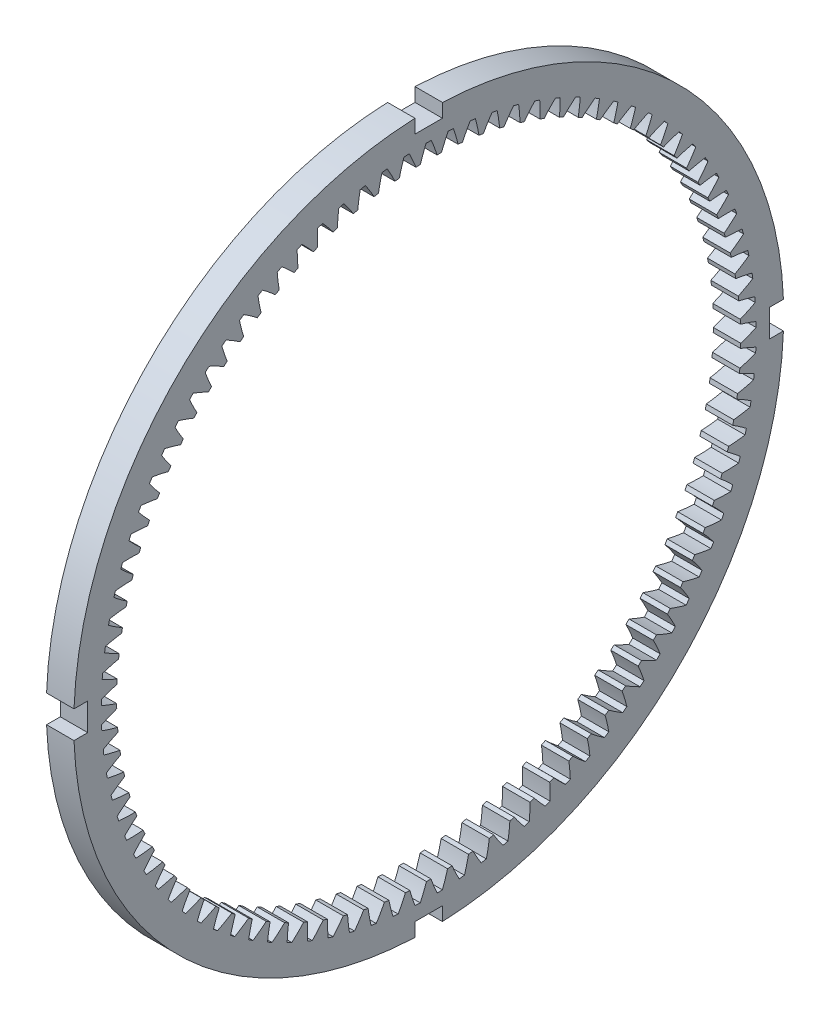
SolidWorks part; units mm, degrees
ref_plane "Plane1" through (0, 0, 0) normal (0, 0, 1) x (1, 0, 0)
ref_plane "Plane2" through (0, 0, 0) normal (0, 1, 0) x (1, 0, 0)
ref_plane "Plane3" through (0, 0, 0) normal (1, 0, 0) x (0, 0, -1)
sketch "HoldingSke" plane through (0, 0, 0) normal (0, 1, 0) x (1, 0, 0)
  line L0 (0, 0) -> (-0.0209, -0.3995)
  line L1 (-15, 0) -> (100, 0) construction
  line L2 (0, 0) -> (-2.1039, 2.3779)
  line L3 (0, 0) -> (-11.863, 4.5341)
  line L4 (0, 0) -> (-0.452, 8.6242)
  line L5 (0, 0) -> (-23.7986, -8.8762)
  line L6 (0, 0) -> (-10.5278, -7.1032)
  line L7 (-2.1039, 2.3779) -> (3.3635, 27.1825)
  line L8 (-76.2, 4.8779) -> (-54.61, 4.8779)
  line L9 (-71.009, 38.7566) -> (-53.1078, 45.2721)
  line L10 (-76.2, 71.12) -> (104.1128, 71.12)
  line L11 (0, 0) -> (-30, 0)
  line L12 (-76.2, 101.6) -> (-76.113, 101.6)
  line L13 (24.9733, 27.94) -> (52.9518, 28.4284)
  line L14 (24.9733, 27.94) -> (24.9743, 27.94)
  line L15 (24.9733, 27.94) -> (100.4006, 29.5858)
  circle A0 centre (0, 0) radius 50
  circle A1 centre (0, 0) radius 12.7
  circle A2 centre (0, 0) radius 12.7
  dimension "MHD" = 25.4
  dimension "Hub_dia" = 25.4
  dimension "Diameter" = 100
  dimension "Num_teeth" = 93
  dimension "Pitch" = 0.4
  dimension "Overall_len" = 25.4
  dimension "Show_teeth" = 93
  dimension "Thickness" = 12.7
  dimension "OAL" = 25.4001
  dimension "T_dim" = 21.59
  dimension "Ap" = 20
  dimension "H" = 19.05
  dimension "Pitch_radius" = 180.3128
  dimension "Width" = 30
  dimension "Backlash" = 0.087
  dimension "Addendum_fac" = 1
  dimension "Dedendum_fac" = 1.25
  dimension "Clearance_fac" = 0.25
  dimension "Dedendum_add" = 0.001
  dimension "Module" = 2.5
sketch "BasProSke" plane through (0, 0, 0) normal (0, 1, 0) x (1, 0, 0)
  line L0 (-10, 0) -> (60, 0) construction
  line L1 (0, 113.75) -> (0, 119.4014)
  line L2 (0, 113.75) -> (30, 113.75)
  line L3 (30, 113.75) -> (30, 119.4014)
  line L4 (30, 119.4014) -> (0, 119.4014)
  dimension "Thickness" = 30
  dimension "Diameter" = 238.8028
  dimension "Inside_diameter" = 227.5
revolve "Base-Revolve" add sketch "BasProSke" angle 360 about L0
sketch "TooCutSke" plane through (0, 0, 0) normal (1, 0, 0) x (0, 0, -1)
  line L3 (2.1809, 116.2295) -> (2.1809, 53.6633) construction
  line L4 (0, 0) -> (0, 59.563) construction
  line L5 (0, 0) -> (-2.3077, 68.2885) construction
  line L6 (-52.5279, 96.5964) -> (34.5007, 99.5374) construction
  circle A0 centre (0, 0) radius 116.25 construction
  circle A1 centre (0, 0) radius 119.376 construction
  circle A2 centre (0, 0) radius 98.3153 construction
  circle A3 centre (0, 0) radius 113.7246 construction
  arc A4 (3.0285, 113.6843) -> (0.949, 119.3722) centre (-52.5279, 96.5964) ccw
  arc A5 (3.0285, 113.6843) -> (-3.0285, 113.6843) centre (0, 0) ccw
  arc A6 (0.949, 119.3722) -> (-0.949, 119.3722) centre (0, 0) ccw
  arc A7 (-0.949, 119.3722) -> (-3.0285, 113.6843) centre (52.5279, 96.5964) ccw
  dimension "Pitch_dia" = 232.5
  dimension "Base_dia" = 196.6307
  dimension "Root_dia" = 238.752
  dimension "Overcut_dia" = 227.4492
  dimension "Flank_rad" = 58.125
  dimension "Half_ang" = 1.935
  dimension "Half_CT" = 2.1809
extrude "ToothCut" cut sketch "TooCutSke" along normal through all
fillet "Breaks" [suppressed] radius 0.25
fillet "RootFillets" [suppressed] radius 0.626
pattern_circular "TeethCuts" count 93 every 3.871 about axis through (-10, 0, 0) along (1, 0, 0) of "RootFillets", "Breaks", "ToothCut"
sketch "草圖2" plane through (0, 0, 0) normal (-1, 0, 0) x (0, 0, 1)
  line L0 (-148.9798, 0) -> (150.1653, 0) construction
  line L1 (0, 146.5311) -> (0, -139.1781) construction
  line L2 (5, 129.3048) -> (5, 124.3048)
  line L3 (-129.3048, 5) -> (-124.3048, 5)
  line L5 (-129.3048, -5) -> (-124.3048, -5)
  line L6 (-124.3048, 5) -> (-124.3048, -5)
  line L7 (5, 124.3048) -> (-5, 124.3048)
  line L8 (-5, 129.3048) -> (-5, 124.3048)
  line L9 (0, 148.9798) -> (0, -150.1653) construction
  line L10 (129.3048, -5) -> (124.3048, -5)
  line L11 (124.3048, -5) -> (124.3048, 5)
  line L12 (129.3048, 5) -> (124.3048, 5)
  line L13 (148.9798, 0) -> (-150.1653, 0) construction
  line L14 (-5, -129.3048) -> (-5, -124.3048)
  line L15 (-5, -124.3048) -> (5, -124.3048)
  line L16 (5, -129.3048) -> (5, -124.3048)
  line L17 (0, -148.9798) -> (0, 150.1653) construction
  circle A0 centre (0, 0) radius 119.4014 construction
  circle A1 centre (0, 0) radius 119.4014
  arc A2 (-129.3048, -5) -> (-5, -129.3048) centre (0, 0) ccw
  circle A3 centre (0, 0) radius 129.4014 construction
  arc A4 (-5, 129.3048) -> (-129.3048, 5) centre (0, 0) ccw
  arc A5 (129.3048, 5) -> (5, 129.3048) centre (0, 0) ccw
  arc A6 (5, -129.3048) -> (129.3048, -5) centre (0, 0) ccw
  point P14 (-124.3048, 0)
  point P36 (0, 0)
  dimension "D2" = 10
  dimension "D3" = 5
  dimension "D1" = 10
  dimension "D4" = 4
extrude "填料-伸長1" add sketch "草圖2" against normal up to surface (30 mm away) up to face at (30, 0, 119.4014)
sketch "草圖3" plane through (0, 0, 0) normal (-1, 0, 0) x (0, 0, 1)
  line L12 (-129.3048, 5) -> (-124.3048, 5)
  line L13 (-124.3048, 5) -> (-124.3048, -5)
  line L14 (-124.3048, -5) -> (-129.3048, -5)
  line L15 (-5, -129.3048) -> (-5, -124.3048)
  line L16 (-5, -124.3048) -> (5, -124.3048)
  line L17 (5, -124.3048) -> (5, -129.3048)
  line L18 (129.3048, -5) -> (124.3048, -5)
  line L19 (124.3048, -5) -> (124.3048, 5)
  line L20 (124.3048, 5) -> (129.3048, 5)
  line L21 (5, 129.3048) -> (5, 124.3048)
  line L22 (5, 124.3048) -> (-5, 124.3048)
  line L23 (-5, 124.3048) -> (-5, 129.3048)
  line L24 (-129.3048, 5) -> (-124.3048, 5)
  line L25 (-124.3048, 5) -> (-124.3048, -5)
  line L26 (-124.3048, -5) -> (-129.3048, -5)
  line L27 (-5, -129.3048) -> (-5, -124.3048)
  line L28 (-5, -124.3048) -> (5, -124.3048)
  line L29 (5, -124.3048) -> (5, -129.3048)
  line L30 (129.3048, -5) -> (124.3048, -5)
  line L31 (124.3048, -5) -> (124.3048, 5)
  line L32 (124.3048, 5) -> (129.3048, 5)
  line L33 (5, 129.3048) -> (5, 124.3048)
  line L34 (5, 124.3048) -> (-5, 124.3048)
  line L35 (-5, 124.3048) -> (-5, 129.3048)
  arc A4 (-5, 129.3048) -> (-129.3048, 5) centre (0, 0) ccw
  arc A5 (-129.3048, -5) -> (-5, -129.3048) centre (0, 0) ccw
  arc A6 (5, -129.3048) -> (129.3048, -5) centre (0, 0) ccw
  arc A7 (129.3048, 5) -> (5, 129.3048) centre (0, 0) ccw
  arc A8 (-5, 129.3048) -> (-129.3048, 5) centre (0, 0) ccw
  arc A9 (-129.3048, -5) -> (-5, -129.3048) centre (0, 0) ccw
  arc A10 (5, -129.3048) -> (129.3048, -5) centre (0, 0) ccw
  arc A11 (129.3048, 5) -> (5, 129.3048) centre (0, 0) ccw
  dimension "D1" = 0
extrude "除料-伸長1" cut sketch "草圖3" against normal blind 20
equation "' \"Module@HoldingSke\" = 6.35"
equation "' \"Num_teeth@HoldingSke\" = 24"
equation "' \"Ap@HoldingSke\" =  14.5"
equation "' \"Ap@HoldingSke\" = 14.5"
equation "' \"Width@HoldingSke\" = 12"
equation "' \"Diameter@HoldingSke\" = 8 * 25.4"
equation "' \"Show_teeth@HoldingSke\" = 100"
equation "' \"Backlash@HoldingSke\" = 0.009 * 25.4"
equation "' \"Addendum_fac@HoldingSke\" = 1.0"
equation "' \"Dedendum_fac@HoldingSke\" = 1.25"
equation "' \"Dedendum_add@HoldingSke\" = 0.00005 * 25.4"
equation "' \"Clearance_fac@HoldingSke\" = 0.25"
equation "\"Pitch@HoldingSke\" = 1 / \"Module@HoldingSke\" "
equation "\"Overcut_dia@TooCutSke\" = (\"Num_teeth@HoldingSke\" - 2 * \"Addendum_fac@HoldingSke\") / \"Pitch@HoldingSke\" - 0.002 * 25.4"
equation "\"Pitch_dia@TooCutSke\" = \"Num_teeth@HoldingSke\" / \"Pitch@HoldingSke\""
equation "\"Base_dia@TooCutSke\" = \"Num_teeth@HoldingSke\" / \"Pitch@HoldingSke\" * cos((\"Ap@HoldingSke\"  * 3.14159265 / 180)) * 0.90"
equation "\"Root_dia@TooCutSke\" = \"Num_teeth@HoldingSke\"  / \"Pitch@HoldingSke\" + 2 *  \"Dedendum_fac@HoldingSke\"/ \"Pitch@HoldingSke\" + \"Dedendum_add@HoldingSke\" * 2"
equation "\"Half_ang@TooCutSke\" = 180 / \"Num_teeth@HoldingSke\""
equation "\"Half_CT@TooCutSke\" = \"Num_teeth@HoldingSke\" / \"Pitch@HoldingSke\" * sin((3.14159265 / 2 / \"Num_teeth@HoldingSke\")) / 2 + 10 * \"Backlash@HoldingSke\" / 4"
equation "\"Flank_rad@TooCutSke\" = \"Num_teeth@HoldingSke\" / \"Pitch@HoldingSke\" / 4"
equation "\"Radius@RootFillets\"= \"Clearance_fac@HoldingSke\" / \"Pitch@HoldingSke\" + \"Dedendum_add@HoldingSke\""
equation "\"Break_rad@Breaks\" = 0.02 / \"Pitch@HoldingSke\" * 5"
equation "\"Num_teeth@TeethCuts\" = int( \"Show_teeth@HoldingSke\" ) + 1"
equation "\"Num_teeth@TeethCuts\" = ((sgn( \"Num_teeth@TeethCuts\" - \"Num_teeth@HoldingSke\" )-1)*( \"Num_teeth@TeethCuts\" - \"Num_teeth@HoldingSke\" ))/-2+ \"Num_teeth@HoldingSke\""
equation "\"Num_teeth@TeethCuts\" = ((sgn( \"Num_teeth@TeethCuts\" - 2.0)+1)*( \"Num_teeth@TeethCuts\" - 2.0))/2 +2.0"
equation "\"Angle@TeethCuts\" = 360.0 / \"Num_teeth@HoldingSke\""
equation "\"Diameter@BasProSke\" = \"Num_teeth@HoldingSke\"  / \"Pitch@HoldingSke\" + 2 *  \"Dedendum_fac@HoldingSke\"/ \"Pitch@HoldingSke\" + \"Dedendum_add@HoldingSke\" * 2 + 0.002 * 25.4"
equation "\"Diameter@BasProSke\" = ((sgn( \"Diameter@BasProSke\"  - \"Diameter@HoldingSke\" )+1)*( \"Diameter@BasProSke\"  - \"Diameter@HoldingSke\" ))/2 + \"Diameter@HoldingSke\""
equation "\"Inside_diameter@BasProSke\" =  (\"Num_teeth@HoldingSke\" - 2 * \"Addendum_fac@HoldingSke\") / \"Pitch@HoldingSke\" "
equation "\"Thickness@BasProSke\"  = \"Width@HoldingSke\""
